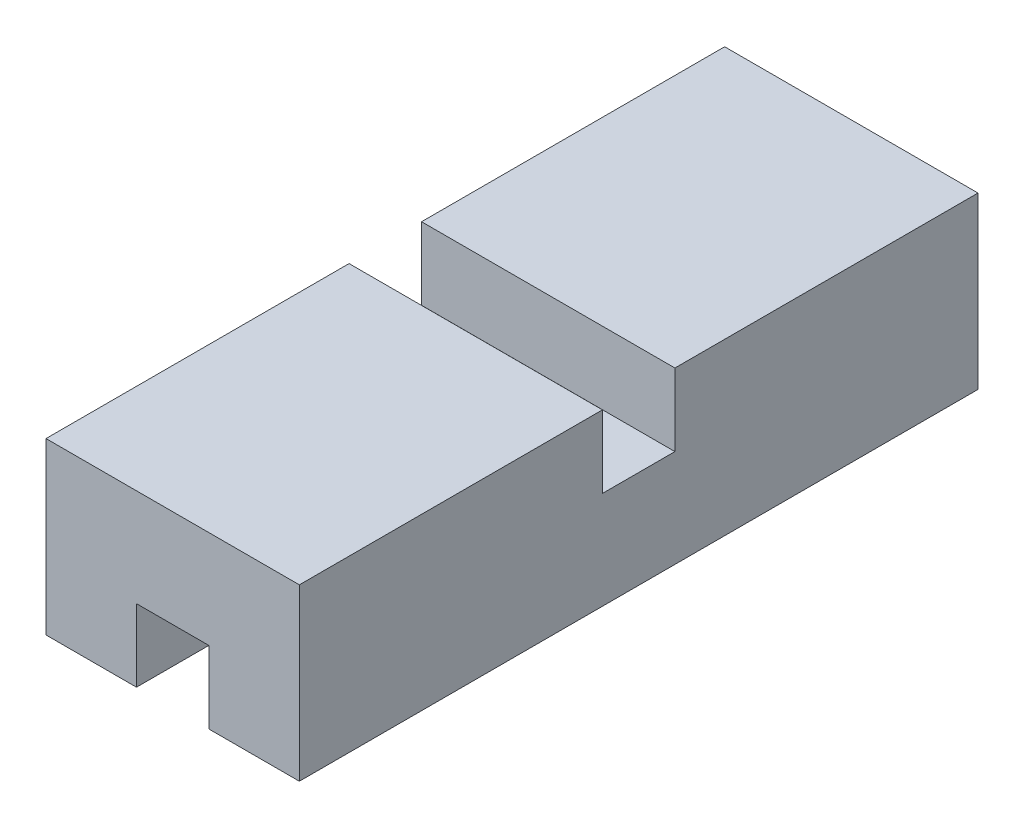
SolidWorks part; units mm, degrees
ref_plane "Front Plane" through (0, 0, 0) normal (0, 0, 1) x (1, 0, 0)
ref_plane "Top Plane" through (0, 0, 0) normal (0, 1, 0) x (1, 0, 0)
ref_plane "Right Plane" through (0, 0, 0) normal (1, 0, 0) x (0, 0, -1)
sketch "Sketch1" plane through (0, 0, 0) normal (0, 1, 0) x (1, 0, 0)
  line L0 (0, 0) -> (0, 75)
  line L1 (0, 75) -> (28, 75)
  line L2 (28, 75) -> (28, 0)
  line L3 (28, 0) -> (0, 0)
  dimension "D1" = 75
  dimension "D2" = 28
extrude "Boss-Extrude1" add sketch "Sketch1" along normal blind 2.8
sketch "Sketch2" plane through (0, 2.8, 0) normal (0, 1, 0) x (1, 0, 0)
  line L0 (28, 0) -> (28, 75) construction
  line L1 (0, 0) -> (28, 0)
  line L2 (0, 0) -> (0, 33.495)
  line L3 (0, 33.495) -> (28, 33.495)
  line L4 (28, 0) -> (28, 33.495)
  line L5 (28, 37.5) -> (0, 37.5) construction
  line L6 (0, 75) -> (28, 75)
  line L7 (0, 75) -> (0, 41.505)
  line L8 (0, 41.505) -> (28, 41.505)
  line L9 (28, 75) -> (28, 41.505)
  line L10 (0, 75) -> (0, 0) construction
  line L11 (28, 41.505) -> (28, 37.5) construction
  line L12 (28, 37.5) -> (28, 33.495) construction
  dimension "D1" = 8.01
extrude "Boss-Extrude2" add sketch "Sketch2" along normal blind 8
sketch "Sketch3" plane through (0, 0, 0) normal (0, -1, 0) x (1, 0, 0)
  line L0 (28, -75) -> (0, -75) construction
  line L1 (0, 0) -> (10, 0)
  line L2 (0, 0) -> (0, -75)
  line L3 (0, -75) -> (10, -75)
  line L4 (10, 0) -> (10, -75)
  line L5 (0, 0) -> (28, 0) construction
  line L7 (18, 0) -> (18, -75)
  line L10 (18, 0) -> (28, 0)
  line L20 (18, -75) -> (28, -75)
  line L22 (28, 0) -> (28, -75)
  point P8 (34.8464, 0)
  point P10 (28, -75)
  dimension "D1" = 8
  dimension "D2" = 10
extrude "Boss-Extrude3" add sketch "Sketch3" along normal blind 8
